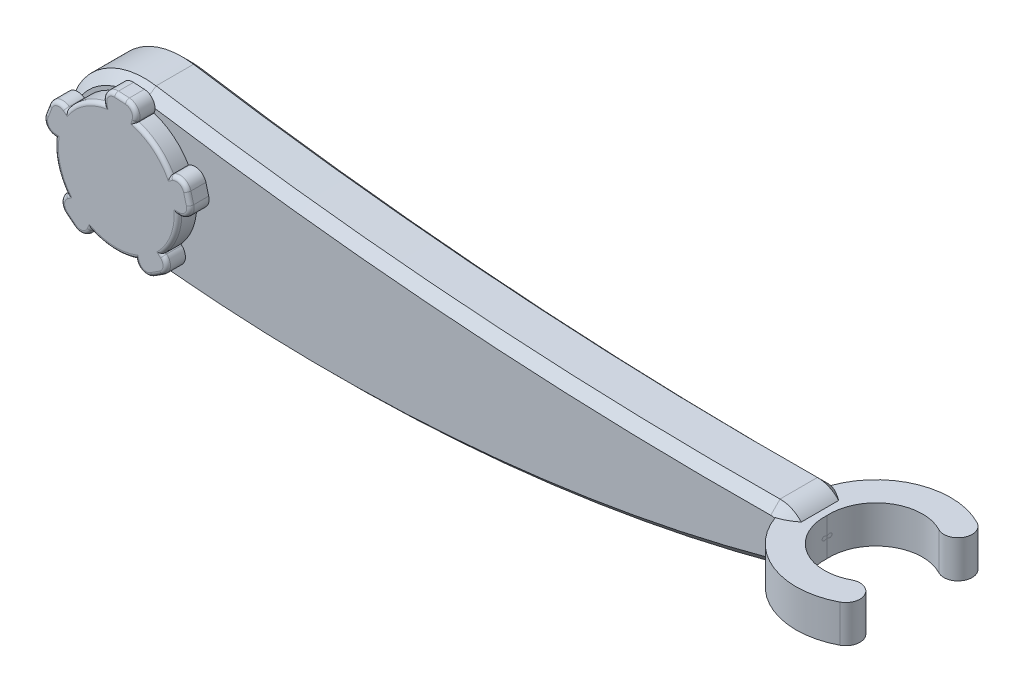
SolidWorks part; units mm, degrees
material "PE High Density"
ref_plane "Front Plane" through (0, 0, 0) normal (0, 0, 1) x (1, 0, 0)
ref_plane "Top Plane" through (0, 0, 0) normal (0, 1, 0) x (1, 0, 0)
ref_plane "Right Plane" through (0, 0, 0) normal (1, 0, 0) x (0, 0, -1)
sketch "Sketch1" plane through (0, 0, 0) normal (0, 0, 1) x (1, 0, 0)
  line L0 (-85, 0) -> (85, 0) construction
  circle A0 centre (85, 0) radius 7.5
  circle A1 centre (-85, 0) radius 20
  arc A2 (84.9221, 7.4996) -> (-81.8718, 19.7538) centre (74.5404, 1007.4457) cw
  arc A3 (-87.4293, -19.8519) -> (85, -7.5) centre (-32.7691, 426.816) ccw
  point P4 (0, 0)
  dimension "D2" = 40
  dimension "D3" = 15
  dimension "D4" = 450
  dimension "D5" = 1000
  dimension "D1" = 170
extrude "Boss-Extrude1" add sketch "Sketch1" along normal mid plane 15 contours A1 L0 A0 A2 | L0 A1 A3 A0 | A1 | A0 region at (-6.4445, 6.0296, 0) region at (-72.1195, -14.5528, 0) region at (-3.3612, -10.4147, 0) region at (79.82, 5.1265, 0)
chamfer "Chamfer1" distance 2.5 angle 45 8 edges at (92.4999, 0.0389, -7.5) (1.2686, 10.1337, -7.5) (-104.806, 2.7792, -7.5) (-0.616, -22.0338, -7.5) (-104.806, 2.7792, 7.5) (1.2686, 10.1337, 7.5) (92.4999, 0.0389, 7.5) (-0.616, -22.0338, 7.5)
sketch "Sketch2" plane through (0, 0, 7.5) normal (0, 0, 1) x (1, 0, 0)
  circle A0 centre (-85, 0) radius 16.5
  dimension "D1" = 33
extrude "Boss-Extrude2" add sketch "Sketch2" along normal blind 5
sketch "Sketch3" plane through (0, 0, 12.5) normal (0, 0, 1) x (1, 0, 0)
  line L0 (-85, 0) -> (-68.2042, 0)
  line L2 (-65.3064, 3.7765) -> (-66.0566, 6.5763)
  line L3 (-70.4544, 8.3979) -> (-85, 0)
  line L4 (-85, 0) -> (-65.6815, 5.1764) construction
  line L5 (-72.5183, -11.2386) -> (-85, 0)
  line L6 (-75.3227, -17.5628) -> (-72.8917, -15.9841)
  line L7 (-85, 0) -> (-79.8098, -15.9738)
  line L8 (-91.8315, -15.3438) -> (-85, 0)
  line L9 (-98.7127, -14.6308) -> (-96.4601, -16.455)
  line L10 (-85, 0) -> (-98.5881, -9.8724)
  line L11 (-101.7038, 1.7556) -> (-85, 0)
  line L12 (-103.1522, 8.5204) -> (-104.191, 5.8143)
  line L13 (-85, 0) -> (-98.5881, 9.8724)
  line L14 (-88.4921, 16.4288) -> (-85, 0)
  line L15 (-82.506, 19.8967) -> (-85.4006, 20.0484)
  line L16 (-85, 0) -> (-79.8098, 15.9738)
  arc A0 (-72.8917, -15.9841) -> (-72.5183, -11.2386) centre (-74.5256, -13.4681) ccw
  arc A1 (-65.3064, 3.7765) -> (-68.2042, 0) centre (-68.2042, 3) cw
  arc A2 (-66.0566, 6.5763) -> (-70.4544, 8.3979) centre (-68.9544, 5.7998) ccw
  arc A3 (-75.3227, -17.5628) -> (-79.8098, -15.9738) centre (-76.9566, -15.0467) cw
  arc A4 (-96.4601, -16.455) -> (-91.8315, -15.3438) centre (-94.5721, -14.1236) ccw
  arc A5 (-98.7127, -14.6308) -> (-98.5881, -9.8724) centre (-96.8248, -12.2994) cw
  arc A6 (-104.191, 5.8143) -> (-101.7038, 1.7556) centre (-101.3903, 4.7392) ccw
  arc A7 (-103.1522, 8.5204) -> (-98.5881, 9.8724) centre (-100.3515, 7.4453) cw
  arc A8 (-85.4006, 20.0484) -> (-88.4921, 16.4288) centre (-85.5576, 17.0526) ccw
  arc A9 (-82.506, 19.8967) -> (-79.8098, 15.9738) centre (-82.663, 16.9009) cw
  circle A10 centre (-85, 0) radius 2
  point P10 (-67.0685, 10.3528)
  point P36 (-85, 0)
  circle M8 centre (-85, 0) radius 16.5
  dimension "D3" = 3
  dimension "D5" = 4
  dimension "D1" = 30
  dimension "D2" = 20
  dimension "D4" = 5
extrude "Boss-Extrude3" add sketch "Sketch3" against normal blind 5 contours A9 L15 A8 L14 L16 M8 | A10 L16 L14 M8 | A10 L4 L3 M8 | L4 A10 L0 M8 | L4 L0 A1 L2 M8 | L4 L2 A2 L3 M8 | A10 L7 L5 M8 | A3 L6 A0 L5 L7 M8 | A10 L10 L8 M8 | A5 L9 A4 L8 L10 M8 | A7 L12 A6 L11 L13 M8 | A10 L13 L11 M8 region at (-73.9827, 1.4505, 12.5) region at (-74.7335, 4.2525, 12.5) region at (-78.9996, -9.2399, 12.5) region at (-91.9334, -8.562, 12.5) region at (-95.2855, 3.9482, 12.5) region at (-84.4234, 11.0022, 12.5) region at (-67.0801, 2.6524, 12.5) region at (-68.1547, 6.6629, 12.5) region at (-75.1988, -15.0925, 12.5) region at (-96.3251, -13.9853, 12.5) region at (-101.8005, 6.4491, 12.5) region at (-84.0582, 17.9711, 12.5)
fillet "Fillet1" radius 1 30 edges at (-88.4613, 16.2841, 12.5) (-87.8388, 19.0009, 12.5) (-83.9533, 19.9726, 12.5) (-80.1906, 18.6001, 12.5) (-79.8555, 15.8331, 12.5) (-74.6162, 12.8229, 12.5) (-70.5825, 8.324, 12.5) (-67.8063, 8.5715, 12.5) (-65.6815, 5.1764, 12.5) (-65.8241, 1.1737, 12.5) (-68.3521, 0, 12.5) (-69.5959, -5.9131, 12.5) (-72.6282, -11.1396, 12.5) (-71.5349, -13.7034, 12.5) (-74.1072, -16.7734, 12.5) (-77.958, -17.8747, 12.5) (-79.8555, -15.8331, 12.5) (-85.8635, -16.4774, 12.5) (-91.7713, -15.2086, 12.5) (-93.8718, -17.0407, 12.5) (-97.5864, -15.5429, 12.5) (-99.8237, -12.2209, 12.5) (-98.4685, -9.7854, 12.5) (-100.9378, -4.2705, 12.5) (-101.5567, 1.7402, 12.5) (-103.9482, 3.1717, 12.5) (-103.6716, 7.1674, 12.5) (-101.2035, 10.3218, 12.5) (-98.4685, 9.7854, 12.5) (-93.9865, 13.8381, 12.5)
sketch "Sketch5" plane through (0, 0, -7.5) normal (0, 0, -1) x (-1, 0, 0)
  circle A0 centre (85, 0) radius 5
  dimension "D1" = 10
extrude "Boss-Extrude4" add sketch "Sketch5" along normal blind 10
sketch "Sketch7" plane through (0, 0, 0) normal (0, 1, 0) x (1, 0, 0)
  line L0 (0, 0) -> (92.5, 0) construction
  line L1 (92.5, -5) -> (92.5, 5) construction
  line L2 (84.9221, -5) -> (84.9221, 5) construction
  arc A0 (84.9221, 0) -> (114.2718, 18.3453) centre (104.9109, 0.6712) cw
  arc A1 (92.5, 0) -> (110.7282, 11.6547) centre (104.9109, 0.6712) cw
  arc A2 (114.2718, 18.3453) -> (110.7282, 11.6547) centre (112.5, 15) cw
  arc A3 (114.2718, -18.3453) -> (110.7282, -11.6547) centre (112.5, -15) ccw
  arc A4 (92.5, 0) -> (110.7282, -11.6547) centre (104.9109, -0.6712) ccw
  arc A5 (84.9221, 0) -> (114.2718, -18.3453) centre (104.9109, -0.6712) ccw
  point P15 (109.7738, -3.3559)
  dimension "D1" = 20
  dimension "D2" = 15
  dimension "D3" = 20
extrude "Boss-Extrude5" add sketch "Sketch7" along normal mid plane 10
